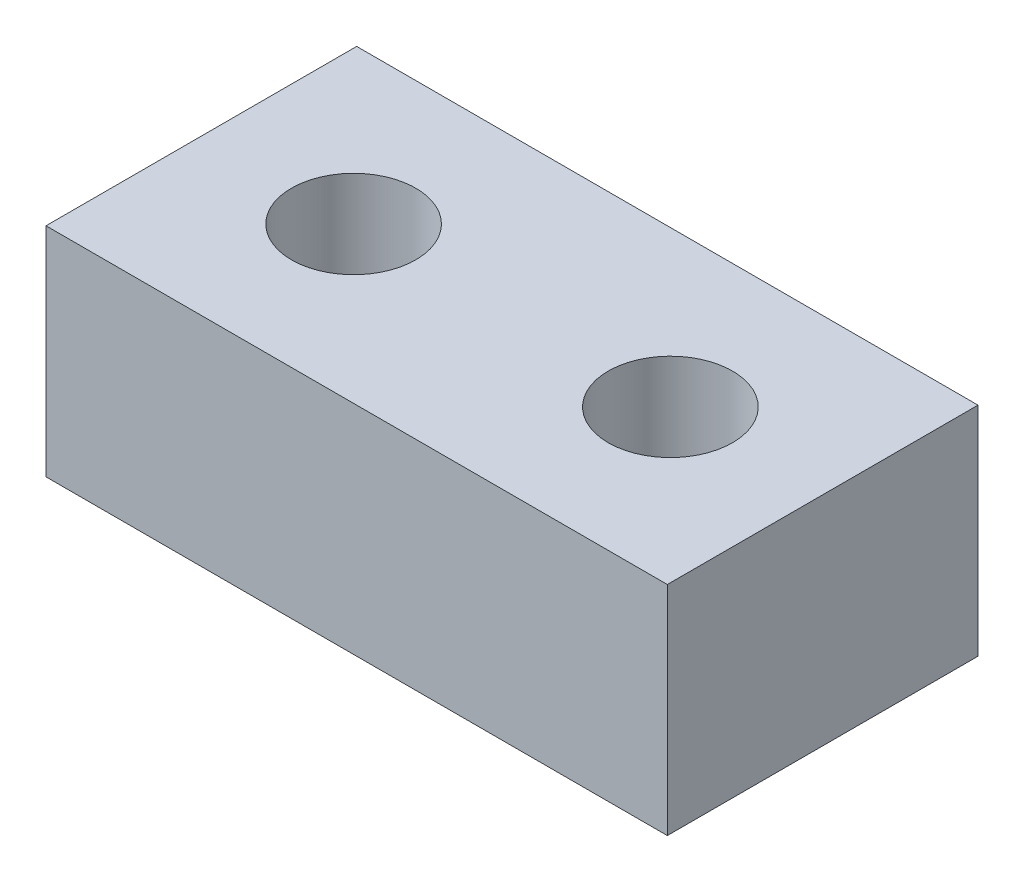
SolidWorks part; units mm, degrees
material "песок"
ref_plane "Front Plane" through (0, 0, 0) normal (0, 0, 1) x (1, 0, 0)
ref_plane "Top Plane" through (0, 0, 0) normal (0, 1, 0) x (1, 0, 0)
ref_plane "Right Plane" through (0, 0, 0) normal (1, 0, 0) x (0, 0, -1)
sketch "Эскиз1" plane through (0, 0, 0) normal (0, 1, 0) x (1, 0, 0)
  line L1 (0, 0) -> (200, 0)
  line L2 (0, 0) -> (0, 100)
  line L3 (0, 100) -> (200, 100)
  line L4 (200, 0) -> (200, 100)
extrude "Бобышка-Вытянуть1" add sketch "Эскиз1" against normal blind 70
sketch "Эскиз3" plane through (0, 0, 0) normal (0, 1, 0) x (1, 0, 0)
  line L0 (0, 50) -> (200, 50)
  line L1 (0, 100) -> (0, 0) construction
  line L2 (200, 0) -> (200, 100) construction
  circle A0 centre (49.0173, 50) radius 20
  circle A1 centre (150.9827, 50) radius 20
extrude "Вырез-Вытянуть1" cut sketch "Эскиз3" against normal blind 40 contours A0
extrude "Вырез-Вытянуть2" cut sketch "Эскиз3<3>" against normal blind 40 contours L0 A1 | L0 A1 region at (150.9827, 0, -58.4883) region at (150.9827, 0, -41.5117)
sketch "Эскиз3<3>" plane through (0, 0, 0) normal (0, 1, 0) x (1, 0, 0) same geometry as "Эскиз3"
